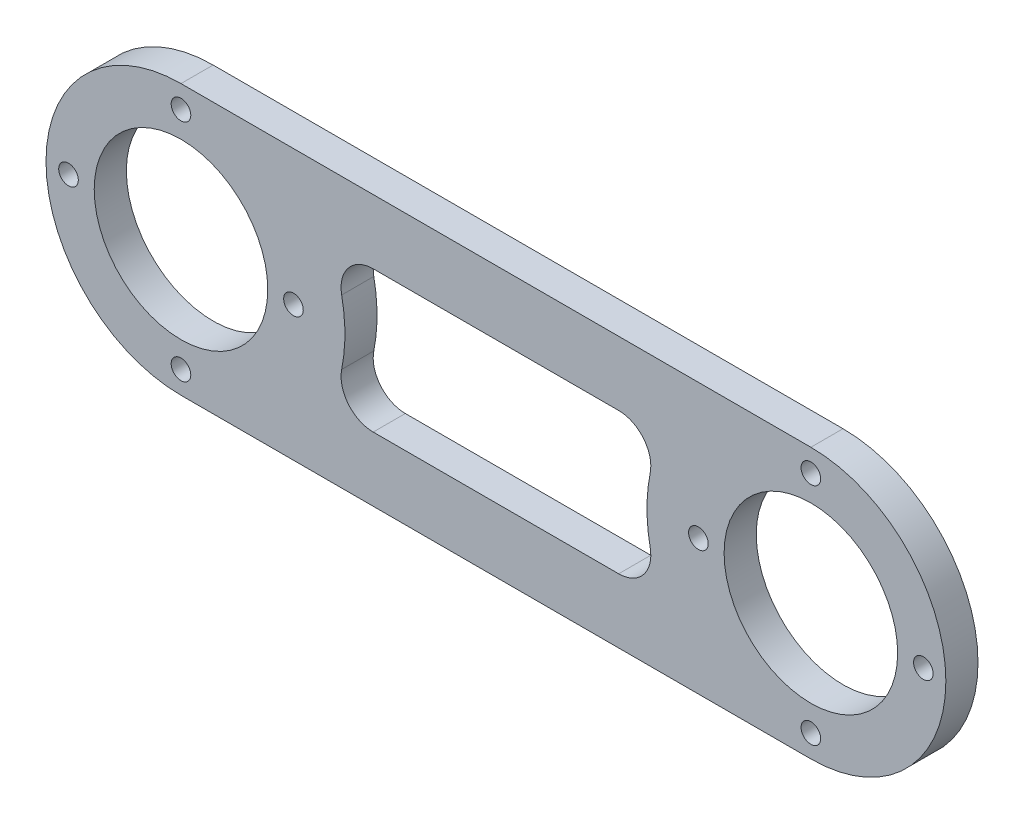
SolidWorks part; units mm, degrees
material "6061 Alloy"
ref_plane "Front Plane" through (0, 0, 0) normal (0, 0, 1) x (1, 0, 0)
ref_plane "Top Plane" through (0, 0, 0) normal (0, 1, 0) x (1, 0, 0)
ref_plane "Right Plane" through (0, 0, 0) normal (1, 0, 0) x (0, 0, -1)
sketch "Sketch1" plane through (0, 0, 0) normal (0, 0, 1) x (1, 0, 0)
  line L0 (49, 26) -> (-49, 26) construction
  line L1 (-49, -16) -> (49, -16) construction
  line L2 (49, 26) -> (-49, 26)
  line L3 (-49, -16) -> (49, -16)
  circle A0 centre (49, 5) radius 21 construction
  circle A3 centre (-66.5, 5) radius 1.5 construction
  circle A4 centre (-49, 22.5) radius 1.5 construction
  circle A5 centre (-31.5, 5) radius 1.5 construction
  circle A6 centre (-49, -12.5) radius 1.5 construction
  circle A8 centre (31.5, 5) radius 1.5 construction
  circle A9 centre (49, 22.5) radius 1.5 construction
  circle A10 centre (66.5, 5) radius 1.5 construction
  circle A11 centre (49, -12.5) radius 1.5 construction
  arc A12 (49, -16) -> (49, 26) centre (49, 5) ccw
  circle A14 centre (-49, 5) radius 13
  circle A15 centre (-66.5, 5) radius 1.5
  circle A16 centre (-49, 22.5) radius 1.5
  circle A17 centre (-31.5, 5) radius 1.5
  circle A18 centre (-49, -12.5) radius 1.5
  circle A19 centre (49, 5) radius 13
  circle A20 centre (31.5, 5) radius 1.5
  circle A21 centre (49, 22.5) radius 1.5
  circle A22 centre (66.5, 5) radius 1.5
  circle A23 centre (49, -12.5) radius 1.5
  arc A24 (-49, 26) -> (-49, -16) centre (-49, 5) ccw
extrude "Boss-Extrude1" add sketch "Sketch1" along normal blind 5
sketch "Sketch2" plane through (0, 0, 0) normal (0, 0, -1) x (-1, 0, 0)
  circle A0 centre (-49, 5) radius 13.5
  circle A1 centre (49, 5) radius 13.5
  dimension "D1" = 27
extrude "Cut-Extrude1" cut sketch "Sketch2" against normal blind 10
sketch "Sketch3" plane through (0, 0, 5) normal (0, 0, 1) x (1, 0, 0)
  line L0 (-49, -16) -> (49, -16) construction
  line L1 (-25.9946, 16) -> (25.9946, 16)
  line L3 (-25.9946, -6) -> (25.9946, -6)
  line L5 (49, 26) -> (-49, 26) construction
  arc A0 (-25.9946, 16) -> (-25.9946, -6) centre (-49, 5) cw
  arc A1 (25.9946, 16) -> (25.9946, -6) centre (49, 5) ccw
  circle A2 centre (-49, 5) radius 13.5 construction
  circle A3 centre (49, 5) radius 13.5 construction
  dimension "D3" = 12
  dimension "D4" = 12
  dimension "D1" = 10
  dimension "D2" = 10
extrude "Cut-Extrude2" cut sketch "Sketch3" against normal blind 10
fillet "Fillet1" radius 5 4 edges at (25.9946, -6, 2.5) (-25.9946, -6, 2.5) (25.9946, 16, 2.5) (-25.9946, 16, 2.5)
sketch "Sketch4" plane through (0, 0, 5) normal (0, 0, 1) x (1, 0, 0)
  circle A0 centre (-49, 22.5) radius 1.525
  circle A1 centre (-66.5, 5) radius 1.525
  circle A2 centre (-31.5, 5) radius 1.525
  circle A3 centre (-49, -12.5) radius 1.525
  circle A4 centre (49, 22.5) radius 1.525
  circle A5 centre (31.5, 5) radius 1.525
  circle A6 centre (66.5, 5) radius 1.525
  circle A7 centre (49, -12.5) radius 1.525
  dimension "D1" = 3.05
extrude "Cut-Extrude3" cut sketch "Sketch4" against normal blind 10
